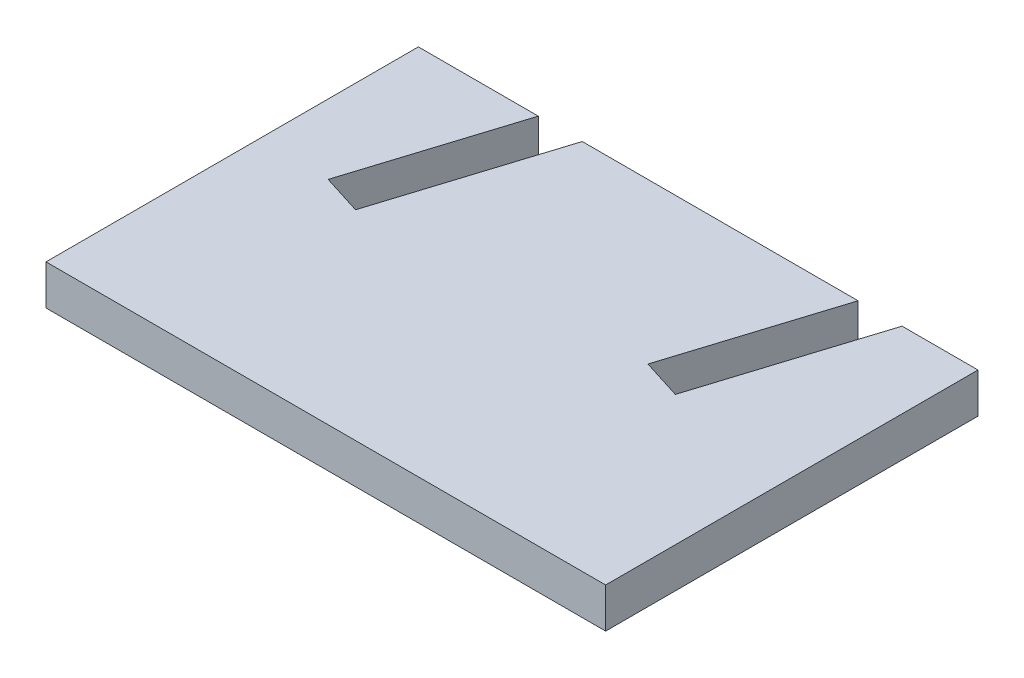
SolidWorks part; units mm, degrees
material "Acrylic (Medium-high impact)"
ref_plane "Front Plane" through (0, 0, 0) normal (0, 0, 1) x (1, 0, 0)
ref_plane "Top Plane" through (0, 0, 0) normal (0, 1, 0) x (1, 0, 0)
ref_plane "Right Plane" through (0, 0, 0) normal (1, 0, 0) x (0, 0, -1)
sketch "Sketch1" plane through (0, 0, 0) normal (0, 1, 0) x (1, 0, 0)
  line L0 (15, 46.575) -> (8.7103, 26.575)
  line L1 (0, 0) -> (70, 0)
  line L2 (0, 0) -> (0, 46.575)
  line L3 (0, 46.575) -> (15, 46.575)
  line L4 (70, 0) -> (70, 46.575)
  line L5 (20.5035, 46.575) -> (55, 46.575)
  line L6 (8.7103, 26.575) -> (13.7185, 25)
  line L7 (20.5035, 46.575) -> (13.7185, 25)
  line L8 (55, 46.575) -> (48.7103, 26.575)
  line L9 (60.5035, 46.575) -> (70, 46.575)
  line L11 (48.7103, 26.575) -> (53.7185, 25)
  line L12 (60.5035, 46.575) -> (53.7185, 25)
  point P5 (11.2144, 25.7875)
  point P8 (51.2144, 25.7875)
  dimension "D1" = 5.25
  dimension "D5" = 40
  dimension "D6" = 25
  dimension "D7" = 20
  dimension "D8" = 70
  dimension "D9" = 15
  dimension "D10" = 17.458
extrude "Boss-Extrude1" add sketch "Sketch1" along normal blind 5
